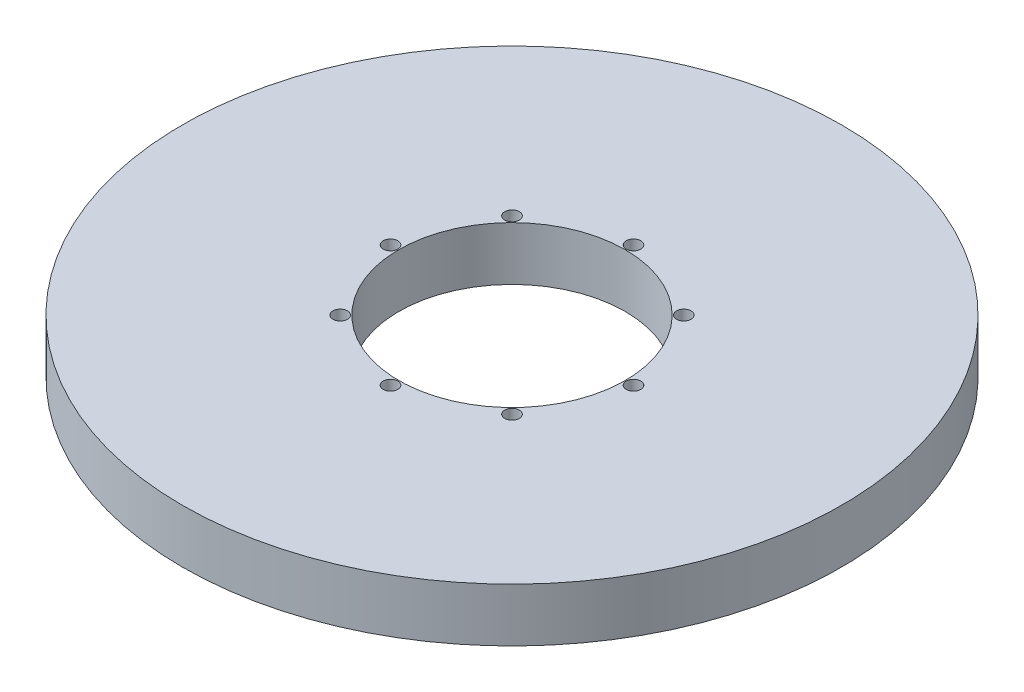
SolidWorks part; units mm, degrees
ref_plane "Front Plane" through (0, 0, 0) normal (0, 0, 1) x (1, 0, 0)
ref_plane "Top Plane" through (0, 0, 0) normal (0, 1, 0) x (1, 0, 0)
ref_plane "Right Plane" through (0, 0, 0) normal (1, 0, 0) x (0, 0, -1)
sketch "Sketch1" plane through (0, 0, 0) normal (0, 1, 0) x (1, 0, 0)
  circle A0 centre (0, 0) radius 80
  dimension "FLANGE_OD" = 160
extrude "Boss-Extrude1" add sketch "Sketch1" along normal blind 13
sketch "Sketch2" plane through (0, 0, 0) normal (0, 1, 0) x (1, 0, 0)
  circle A0 centre (0, 0) radius 27.5
  dimension "BORE_D" = 55
extrude "Cut-Extrude1" cut sketch "Sketch2" along normal through all
sketch "Sketch3" plane through (0, 13, 0) normal (0, 1, 0) x (1, 0, 0)
  circle A0 centre (0, 0) radius 29.4924 construction
  circle A1 centre (-29.4924, 0) radius 1.7732
  dimension "BOLT_D" = 3.5465
  dimension "BOLT_PCD" = 58.9847
extrude "Cut-Extrude2" cut sketch "Sketch3" against normal blind 12.7441
pattern_circular "CirPattern1" count 8 over 360 about axis through (0, 0, 0) along (0, 1, 0) of "Cut-Extrude2"
